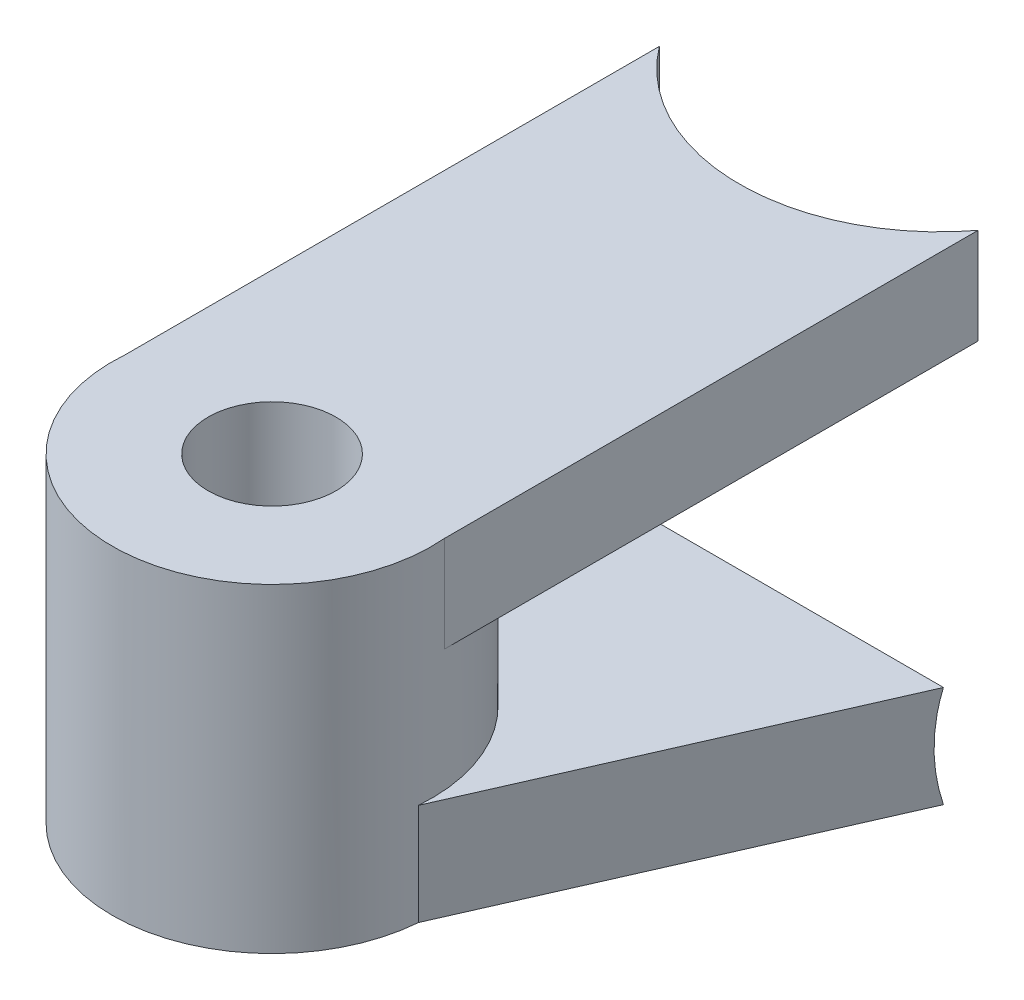
SolidWorks part; units mm, degrees
ref_plane "Front Plane" through (0, 0, 0) normal (0, 0, 1) x (1, 0, 0)
ref_plane "Top Plane" through (0, 0, 0) normal (0, 1, 0) x (1, 0, 0)
ref_plane "Right Plane" through (0, 0, 0) normal (1, 0, 0) x (0, 0, -1)
sketch "Sketch1" plane through (0, 0, 0) normal (0, 1, 0) x (1, 0, 0)
  line L0 (0, 0) -> (40, 0)
  line L4 (0, 0) -> (10.0326, -22.8063)
  line L5 (29.9674, -22.8063) -> (40, 0)
  line L6 (20, 0) -> (20, -17.1488) construction
  line L7 (10.0326, -22.8063) -> (29.9674, -22.8063) construction
  circle A0 centre (20, -22) radius 4
  circle A1 centre (20, -22) radius 10
  dimension "D2" = 20
  dimension "D3" = 8
  dimension "D1" = 40
  dimension "D4" = 22
extrude "Boss-Extrude1" add sketch "Sketch1" along normal blind 6.35 contours A1 L5 L0 L4 region at (20, 0, 7.3958)
extrude "Boss-Extrude2" add sketch "Sketch1<3>" along normal blind 20 contours A1 A0 region at (19.6079, 0, 12.2908)
sketch "Sketch1<3>" plane through (0, 0, 0) normal (0, 1, 0) x (1, 0, 0) same geometry as "Sketch1"
ref_plane "Plane1" through (0, 10, 0) normal (0, 1, 0) x (1, 0, 0)
sketch "Sketch2" plane through (0, 0, 0) normal (1, 0, 0) x (0, 0, -1)
  line L0 (0, 3.175) -> (21.8325, 3.175) construction
  line L1 (0, 6.35) -> (0, 0) construction
  circle A0 centre (12.0901, 3.175) radius 12.5
  dimension "D1" = 25
extrude "Cut-Extrude1" cut sketch "Sketch2" along normal through all
sketch "Sketch3" plane through (0, 20, 0) normal (0, 1, 0) x (1, 0, 0)
  line L0 (20, 12.1937) -> (20, 19.7369) construction
  line L1 (10.0326, -22.8063) -> (29.9674, -22.8063)
  line L2 (10.0326, -22.8063) -> (10.0326, 12.1937)
  line L3 (10.0326, 12.1937) -> (29.9674, 12.1937)
  line L4 (29.9674, -22.8063) -> (29.9674, 12.1937)
  line L6 (20, 19.7369) -> (20, -18)
  circle A1 centre (20, -22) radius 4
  circle A2 centre (20, 19.7369) radius 12.5
  circle M8 centre (20, -22) radius 10
  dimension "D1" = 25
  dimension "D2" = 35
extrude "Boss-Extrude3" add sketch "Sketch3" against normal blind 6 contours A2 L2 L4 M8 | A2 L2 L6 M8 | A2 L2 M8 | A2 L4 M8 region at (14.5908, 20, 2.7572) region at (25.4092, 20, 2.7572)
